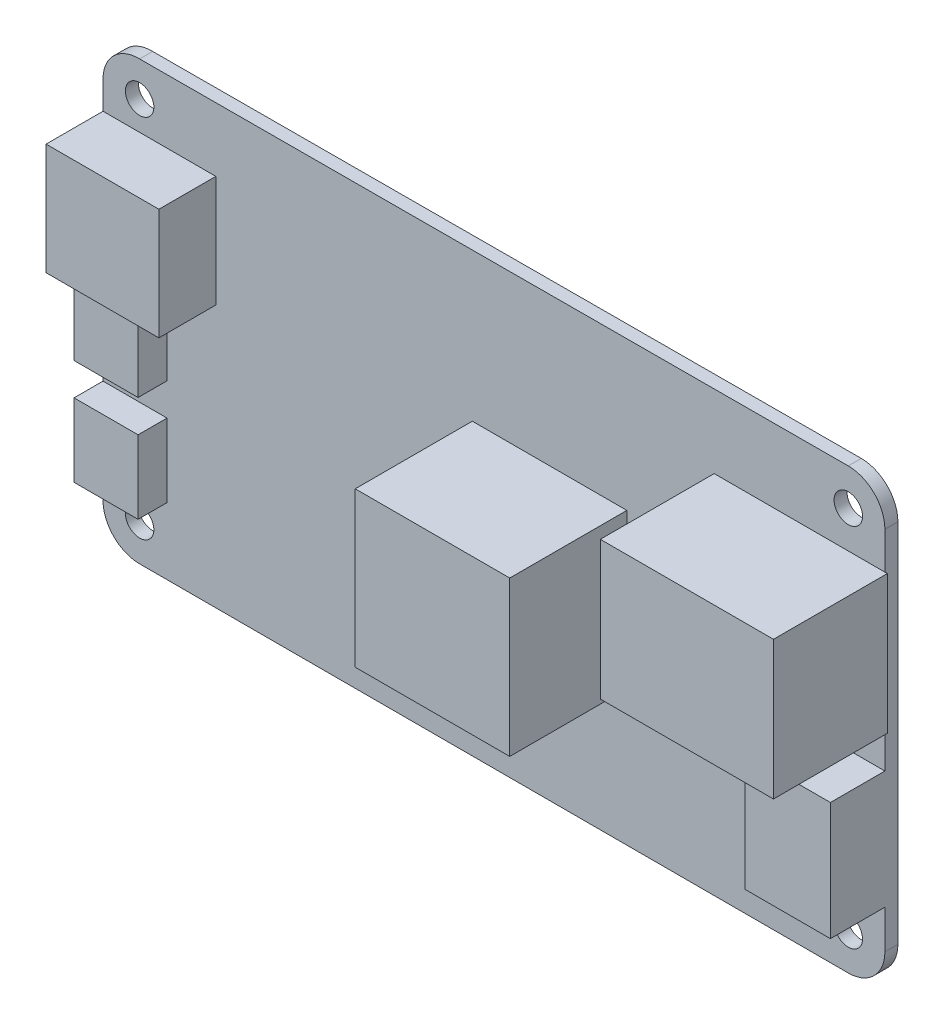
SolidWorks part; units mm, degrees
ref_plane "Front Plane" through (0, 0, 0) normal (0, 0, 1) x (1, 0, 0)
ref_plane "Top Plane" through (0, 0, 0) normal (0, 1, 0) x (1, 0, 0)
ref_plane "Right Plane" through (0, 0, 0) normal (1, 0, 0) x (0, 0, -1)
sketch "pcb" plane through (0, 0, -31.4284) normal (0, 0, 1) x (1, 0, 0)
  line L0 (91.8508, -91.4513) -> (91.8508, -136.4513)
  line L1 (87.3508, -140.9513) -> (0.2108, -140.9513)
  line L2 (-4.2892, -136.4513) -> (-4.2892, -91.4513)
  line L3 (87.3508, -86.9513) -> (0.2108, -87.1809)
  line L4 (-242.3949, -87.1809) -> (70.1051, -87.1809) construction
  circle A0 centre (87.3508, -136.4513) radius 1.75
  circle A1 centre (87.3508, -91.4513) radius 1.75
  circle A2 centre (0.2108, -91.4513) radius 1.75
  circle A3 centre (0.2108, -136.4513) radius 1.75
  arc A4 (87.3508, -140.9513) -> (91.8508, -136.4513) centre (87.3508, -136.4513) ccw
  arc A5 (87.3508, -86.9513) -> (91.8508, -91.4513) centre (87.3508, -91.4513) cw
  circle A6 centre (87.3508, -136.4513) radius 4.5 construction
  arc A7 (91.6807, -137.6771) -> (91.6807, -135.2256) centre (87.3508, -136.4513) ccw construction
  arc A8 (-4.2892, -136.4513) -> (0.2108, -140.9513) centre (0.2108, -136.4513) ccw
  circle A9 centre (0.2108, -136.4513) radius 4.5 construction
  circle A12 centre (87.3508, -91.4513) radius 4.5 construction
  arc A13 (-2.805, -88.1114) -> (3.2266, -88.1114) centre (0.2108, -91.4513) ccw construction
  arc A14 (-4.2892, -91.4513) -> (0.2108, -87.1809) centre (0.096, -91.5661) cw
  dimension "D1" = 3.5
  dimension "D2" = 4.3867
extrude "board" add sketch "pcb" along normal blind 1.6
sketch "gige" plane through (0, 0, -29.8284) normal (0, 0, 1) x (1, 0, 0)
  line L0 (87.3508, -91.4513) -> (80.434, -91.4513) construction
  line L1 (70.8608, -113.0213) -> (92.1508, -113.0213)
  line L2 (70.8608, -113.0213) -> (70.8608, -96.0113)
  line L3 (70.8608, -96.0113) -> (92.1508, -96.0113)
  line L4 (92.1508, -113.0213) -> (92.1508, -96.0113)
  line L5 (91.8508, -136.4513) -> (91.8508, -91.4513) construction
  dimension "D1" = 4.56
  dimension "D2" = 20.99
  dimension "D3" = 0.3
  dimension "D4" = 17.01
extrude "ethernetport" add sketch "gige" along normal blind 14
sketch "hdmi" plane through (0, 0, -29.8284) normal (0, 0, 1) x (1, 0, 0)
  line L0 (87.3508, -136.4513) -> (81.831, -136.4513) construction
  line L1 (91.8508, -131.6913) -> (81.3508, -131.6913)
  line L2 (91.8508, -131.6913) -> (91.8508, -117.1913)
  line L3 (91.8508, -117.1913) -> (81.3508, -117.1913)
  line L4 (81.3508, -131.6913) -> (81.3508, -117.1913)
  line L5 (91.8508, -136.4513) -> (91.8508, -113.0213) construction
  dimension "D1" = 4.76
  dimension "D2" = 0
  dimension "D3" = 14.5
  dimension "D4" = 10.5
extrude "hdmiport" add sketch "hdmi" along normal blind 6.7
sketch "Sketch9" plane through (0, 0, -29.8284) normal (0, 0, 1) x (1, 0, 0)
  line L0 (91.8508, -117.1913) -> (91.8508, -113.0213) construction
  line L1 (60.1208, -124.3025) -> (41.1208, -124.3025)
  line L2 (60.1208, -124.3025) -> (60.1208, -105.3025)
  line L3 (60.1208, -105.3025) -> (41.1208, -105.3025)
  line L4 (41.1208, -124.3025) -> (41.1208, -105.3025)
  line L5 (81.6051, -141.0625) -> (-238.936, -141.0625) construction
  dimension "D1" = 31.73
  dimension "D2" = 19
  dimension "D3" = 19
  dimension "D4" = 16.76
extrude "FPGAandFan" add sketch "Sketch9" along normal blind 14.4
sketch "Sketch10" plane through (0, 0, -29.8284) normal (0, 0, 1) x (1, 0, 0)
  line L0 (-4.2892, -91.4513) -> (-4.2892, -136.4513) construction
  line L1 (3.5808, -110.7713) -> (-4.2892, -110.7713)
  line L2 (3.5808, -110.7713) -> (3.5808, -119.7713)
  line L3 (3.5808, -119.7713) -> (-4.2892, -119.7713)
  line L4 (-4.2892, -110.7713) -> (-4.2892, -119.7713)
  line L5 (3.5808, -123.7413) -> (-4.2892, -123.7413)
  line L6 (3.5808, -123.7413) -> (3.5808, -132.7413)
  line L7 (3.5808, -132.7413) -> (-4.2892, -132.7413)
  line L8 (-4.2892, -123.7413) -> (-4.2892, -132.7413)
  point P8 (0.2108, -136.4513)
  dimension "D1" = 3.71
  dimension "D2" = 16.68
  dimension "D3" = 0
  dimension "D4" = 0
  dimension "D5" = 9
  dimension "D6" = 9
  dimension "D7" = 7.87
  dimension "D8" = 7.87
extrude "usbc" add sketch "Sketch10" along normal blind 3.56
sketch "Sketch11" plane through (0, 0, -29.8284) normal (0, 0, 1) x (1, 0, 0)
  line L1 (9.5808, -108.7009) -> (-4.2892, -108.7009)
  line L2 (9.5808, -108.7009) -> (9.5808, -95.0009)
  line L3 (9.5808, -95.0009) -> (-4.2892, -95.0009)
  line L4 (-4.2892, -108.7009) -> (-4.2892, -95.0009)
  line L5 (-4.2892, -91.4513) -> (-4.2892, -110.7713) construction
  point P4 (0.2108, -91.4513)
  dimension "D1" = 7.82
  dimension "D2" = 13.7
  dimension "D3" = 0
  dimension "D4" = 13.87
extrude "USBA" add sketch "Sketch11" along normal blind 7
